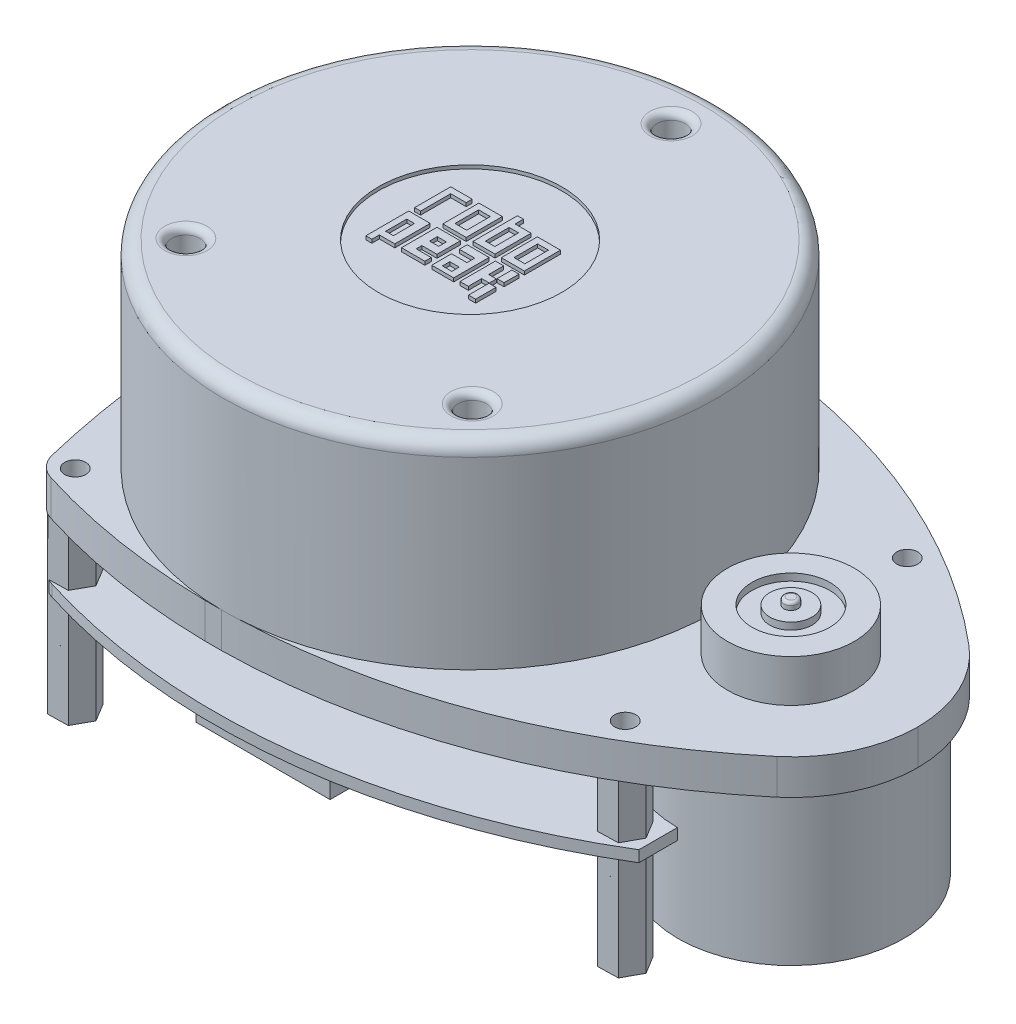
SolidWorks part; units mm, degrees
ref_plane "Спереди" through (0, 0, 0) normal (0, 0, 1) x (1, 0, 0)
ref_plane "Сверху" through (0, 0, 0) normal (0, 1, 0) x (1, 0, 0)
ref_plane "Справа" through (0, 0, 0) normal (1, 0, 0) x (0, 0, -1)
sketch "Эскиз1" plane through (0, 0, 0) normal (0, 1, 0) x (1, 0, 0)
  line L1 (-49.25, 35) -> (49.25, 35)
  line L2 (-49.25, 35) -> (-49.25, -35)
  line L3 (-49.25, -35) -> (49.25, -35)
  line L4 (49.25, 35) -> (49.25, -35)
  line L5 (-49.25, 35) -> (49.25, -35) construction
  line L6 (-49.25, -35) -> (49.25, 35) construction
  point P0 (0, 0)
  dimension "D1" = 98.5
  dimension "D2" = 70
extrude "Бобышка-Вытянуть1" add sketch "Эскиз1" along normal blind 5
sketch "Эскиз2" plane through (0, 5, 0) normal (0, 1, 0) x (1, 0, 0)
  line L0 (-49.25, 35) -> (-49.25, -35) construction
  circle A0 centre (-14.25, 0) radius 35
  point P2 (-49.25, 0)
  point P3 (-49.25, 0)
extrude "Бобышка-Вытянуть2" add sketch "Эскиз2" along normal blind 28.1
sketch "Эскиз3" plane through (0, 33.1, 0) normal (0, 1, 0) x (1, 0, 0)
  line L0 (-14.25, 0) -> (-14.25, 50000) construction
  line L1 (-14.25, -20) -> (-26.2883, -20) construction
  line L2 (-49.25, -35) -> (-14.25, -35) construction
  circle A0 centre (-14.25, 28.5) radius 2
  circle A1 centre (-34.5539, -20) radius 2
  circle A2 centre (6.0539, -20) radius 2
  arc A3 (-49.25, 0) -> (-14.25, -35) centre (-14.25, 0) ccw construction
  circle A4 centre (-14.25, 0) radius 35 construction
  dimension "D2" = 4
  dimension "D1" = 6.5
  dimension "D3" = 15
  dimension "D4" = 28.5
  dimension "D5" = 28.5
extrude "Вырез-Вытянуть1" cut sketch "Эскиз3" against normal blind 5
fillet "Скругление1" radius 2 1 edges at (-14.25, 33.1, 35)
fillet "Скругление2" radius 1 3 edges at (6.0539, 33.1, 22) (-34.5539, 33.1, 22) (-14.25, 33.1, -26.5)
sketch "Эскиз4" plane through (0, 33.1, 0) normal (0, 1, 0) x (1, 0, 0)
  line L0 (-22.1152, -6.9149) -> (-22.1152, -0.8316)
  line L1 (-22.1152, -0.8316) -> (-19.0735, -0.8316)
  line L2 (-19.0735, -0.8316) -> (-19.0735, -5.8538)
  line L3 (-19.0735, -5.8538) -> (-21.2663, -5.8538)
  line L4 (-21.2663, -5.8538) -> (-21.2663, -6.9149)
  line L5 (-21.2663, -6.9149) -> (-22.1152, -6.9149)
  line L6 (-22.1152, 0) -> (-22.1152, 5.1201)
  line L7 (-22.1152, 5.1201) -> (-19.0735, 5.1201)
  line L8 (-19.0735, 5.1201) -> (-19.0735, 4.2707)
  line L9 (-19.0735, 4.2707) -> (-21.2663, 4.2707)
  line L10 (-21.2663, 4.2707) -> (-21.2663, 0)
  line L11 (-21.2663, 0) -> (-22.1152, 0)
  line L12 (-21.2663, -1.9579) -> (-20.1699, -1.9579)
  line L13 (-20.1699, -1.9579) -> (-20.1699, -4.9509)
  line L14 (-20.1699, -4.9509) -> (-21.2663, -4.9509)
  line L15 (-21.2663, -4.9509) -> (-21.2663, -1.9579)
  line L16 (-13.8296, 0) -> (-13.8296, 6.293)
  line L17 (-18.1168, 0) -> (-14.8003, 0)
  line L18 (-18.1168, 0) -> (-18.1168, 5.1201)
  line L19 (-18.1168, 5.1201) -> (-14.8003, 5.1201)
  line L20 (-14.8003, 0) -> (-14.8003, 5.1201)
  line L21 (-9.8255, 5.1201) -> (-6.5494, 5.1201)
  line L22 (-9.8255, 5.1201) -> (-9.8255, 0)
  line L23 (-9.8255, 0) -> (-6.5494, 0)
  line L24 (-6.5494, 5.1201) -> (-6.5494, 0)
  line L25 (-8.9357, 4.2707) -> (-7.3988, 4.2707)
  line L26 (-8.9357, 4.2707) -> (-8.9357, 0.9137)
  line L27 (-8.9357, 0.9137) -> (-7.3988, 0.9137)
  line L28 (-7.3988, 4.2707) -> (-7.3988, 0.9137)
  line L29 (-17.3079, 4.2707) -> (-15.6497, 4.2707)
  line L30 (-17.3079, 4.2707) -> (-17.3079, 0.9137)
  line L31 (-17.3079, 0.9137) -> (-15.6497, 0.9137)
  line L32 (-15.6497, 4.2707) -> (-15.6497, 0.9137)
  line L33 (-12.9802, 4.2707) -> (-11.6455, 4.2707)
  line L34 (-12.9802, 4.2707) -> (-12.9802, 0.9137)
  line L35 (-12.9802, 0.9137) -> (-11.6455, 0.9137)
  line L36 (-11.6455, 4.2707) -> (-11.6455, 0.9137)
  line L37 (-12.9802, -4.142) -> (-11.6455, -4.142)
  line L38 (-12.9802, -4.142) -> (-12.9802, -5.1936)
  line L39 (-12.9802, -5.1936) -> (-11.6455, -5.1936)
  line L40 (-11.6455, -4.142) -> (-11.6455, -5.1936)
  line L41 (-16.9439, -1.9579) -> (-15.6497, -1.9579)
  line L42 (-16.9439, -1.9579) -> (-16.9439, -3.0499)
  line L43 (-16.9439, -3.0499) -> (-15.6497, -3.0499)
  line L44 (-15.6497, -1.9579) -> (-15.6497, -3.0499)
  line L46 (-7.5508, -0.7643) -> (-6.5494, -0.7643)
  line L47 (-7.5508, -0.7643) -> (-7.5508, -2.8858)
  line L48 (-7.5508, -2.8858) -> (-6.5494, -2.8858)
  line L49 (-6.5494, -0.7643) -> (-6.5494, -2.8858)
  line L50 (-6.5494, -6.9149) -> (-7.5508, -6.9149)
  line L51 (-6.5494, -6.9149) -> (-6.5494, -4.0216)
  line L52 (-6.5494, -4.0216) -> (-7.5508, -4.0216)
  line L53 (-13.8296, 6.293) -> (-12.9802, 6.293)
  line L54 (-12.9802, 6.293) -> (-12.9802, 5.1201)
  line L55 (-12.9802, 5.1201) -> (-10.7153, 5.1201)
  line L56 (-10.7153, 5.1201) -> (-10.7153, 0)
  line L57 (-10.7153, 0) -> (-13.8296, 0)
  line L58 (-9.8255, -0.8316) -> (-8.6437, -0.8316)
  line L59 (-8.6437, -0.8316) -> (-8.6437, -2.9608)
  line L60 (-8.6437, -2.9608) -> (-7.5508, -2.9608)
  line L61 (-9.8255, -0.8316) -> (-9.8255, -5.8538)
  line L62 (-9.8255, -5.8538) -> (-8.6437, -5.8538)
  line L63 (-8.6437, -5.8538) -> (-8.6437, -3.9573)
  line L64 (-8.6437, -3.9573) -> (-7.5508, -3.9573)
  line L65 (-7.5508, -2.9608) -> (-7.5508, -3.9573)
  line L66 (-13.8296, -0.8316) -> (-10.7153, -0.8316)
  line L67 (-10.7153, -0.8316) -> (-10.7153, -5.8538)
  line L68 (-10.7153, -5.8538) -> (-13.8296, -5.8538)
  line L69 (-13.8296, -5.8538) -> (-13.8296, -3.0499)
  line L70 (-13.8296, -3.0499) -> (-11.6455, -3.0499)
  line L71 (-11.6455, -3.0499) -> (-11.6455, -1.9408)
  line L72 (-11.6455, -1.9408) -> (-13.8296, -1.9408)
  line L73 (-13.8296, -1.9408) -> (-13.8296, -0.8316)
  line L74 (-18.1168, -0.8316) -> (-14.8003, -0.8316)
  line L75 (-14.8003, -0.8316) -> (-14.8003, -4.142)
  line L76 (-14.8003, -4.142) -> (-16.9439, -4.142)
  line L77 (-16.9439, -4.142) -> (-16.9439, -4.9509)
  line L78 (-16.9439, -4.9509) -> (-14.8003, -4.9509)
  line L79 (-14.8003, -4.9509) -> (-14.8003, -5.8538)
  line L80 (-14.8003, -5.8538) -> (-18.1168, -5.8538)
  line L81 (-18.1168, -5.8538) -> (-18.1168, -0.8316)
  line L82 (-7.5508, -6.9149) -> (-7.5508, -4.0216)
  circle A0 centre (-14.25, 0) radius 13
  dimension "D1" = 26
extrude "Вырез-Вытянуть3" cut sketch "Эскиз4" against normal blind 0.5 contours A0 L50 L82 L52 L51 L72 L73 L66 L67 L68 L69 L70 L71 L56 L57 L16 L53 L54 L55 L10 L11 L6 L7 L8 L9 L4 L5 L0 L1 L2 L3 L20 L17 L18 L19 L21 L24 L23 L22 L46 L49 L48 L47 | L32 L29 L30 L31 | L36 L33 L34 L35 | L28 L25 L26 L27 | L44 L41 L42 L43 | L15 L14 L13 L12 | L37 L40 L39 L38 region at (-20.7181, 33.1, 3.4544) region at (-8.1672, 33.1, -2.5922) region at (-16.4788, 33.1, -2.5922) region at (-12.3129, 33.1, -2.5922) region at (-16.2968, 33.1, 2.5039) region at (-14.2871, 33.1, -0.0991)
sketch "Эскиз5" plane through (0, 5, 0) normal (0, 1, 0) x (1, 0, 0)
  line L0 (-42.25, 30.7255) -> (-42.25, -39.5827) construction
  line L1 (27.75, 26.9972) -> (27.75, -49973.0028) construction
  line L2 (-49.25, 0) -> (49950.75, 0) construction
  circle A0 centre (-14.25, 0) radius 33 construction
  circle A1 centre (-42.25, 28) radius 1.25
  circle A2 centre (27.75, 20) radius 1.25
  circle A3 centre (27.75, -20) radius 1.25
  circle A4 centre (-42.25, -28) radius 1.25
  point P4 (-14.25, 33)
  dimension "D1" = 28
  dimension "D3" = 2.5
  dimension "D2" = 42
  dimension "D4" = 28
  dimension "D5" = 20
extrude "Вырез-Вытянуть4" cut sketch "Эскиз5" against normal blind 5
sketch "Эскиз6" plane through (0, 5, 0) normal (0, 1, 0) x (1, 0, 0)
  line L0 (49.25, 0) -> (50049.25, 0) construction
  line L1 (49.25, -35) -> (49.25, 35) construction
  circle A0 centre (31.25, 0) radius 9
  arc A1 (-14.25, -35) -> (-14.25, 35) centre (-14.25, 0) ccw construction
  point P4 (49.25, 0)
  dimension "D1" = 18
  dimension "D2" = 45.5
extrude "Бобышка-Вытянуть3" add sketch "Эскиз6" along normal blind 7
sketch "Эскиз7" plane through (0, 12, 0) normal (0, 1, 0) x (1, 0, 0)
  circle A0 centre (31.25, 0) radius 9
  circle A1 centre (31.25, 0) radius 0.9935
extrude "Вырез-Вытянуть5" cut sketch "Эскиз7" against normal blind 1
sketch "Эскиз8" plane through (0, 11, 0) normal (0, 1, 0) x (1, 0, 0)
  circle A0 centre (31.25, 0) radius 3.0011
  circle A1 centre (31.25, 0) radius 5.5217
extrude "Вырез-Вытянуть6" cut sketch "Эскиз8" against normal blind 1
fillet "Скругление3" radius 0.4 1 edges at (31.25, 12, 0.9935)
sketch "Эскиз9" plane through (0, 5, 0) normal (0, 1, 0) x (1, 0, 0)
  circle A0 centre (31.25, 0) radius 16
  dimension "D1" = 32
extrude "Бобышка-Вытянуть4" add sketch "Эскиз9" against normal blind 27
sketch "Эскиз10" plane through (0, 0, 0) normal (0, -1, 0) x (1, 0, 0)
  line L0 (-49.25, 0) -> (49950.75, 0) construction
  line L1 (-40.8546, 25.4729) -> (-39.3638, 27.9449)
  line L2 (-39.3638, 27.9449) -> (-40.7592, 30.472)
  line L3 (-40.7592, 30.472) -> (-43.6454, 30.5271)
  line L4 (-43.6454, 30.5271) -> (-45.1362, 28.0551)
  line L5 (-45.1362, 28.0551) -> (-43.7408, 25.528)
  line L6 (-43.7408, 25.528) -> (-40.8546, 25.4729)
  line L7 (29.2571, 22.4621) -> (26.3713, 22.5363)
  line L8 (26.3713, 22.5363) -> (24.8642, 20.0742)
  line L9 (24.8642, 20.0742) -> (26.2429, 17.5379)
  line L10 (26.2429, 17.5379) -> (29.1287, 17.4637)
  line L11 (29.1287, 17.4637) -> (30.6358, 19.9258)
  line L12 (30.6358, 19.9258) -> (29.2571, 22.4621)
  line L13 (30.6358, -19.9258) -> (29.2571, -22.4621)
  line L14 (29.1287, -17.4637) -> (30.6358, -19.9258)
  line L15 (26.2429, -17.5379) -> (29.1287, -17.4637)
  line L16 (24.8642, -20.0742) -> (26.2429, -17.5379)
  line L17 (26.3713, -22.5363) -> (24.8642, -20.0742)
  line L18 (29.2571, -22.4621) -> (26.3713, -22.5363)
  line L19 (-43.7408, -25.528) -> (-40.8546, -25.4729)
  line L20 (-45.1362, -28.0551) -> (-43.7408, -25.528)
  line L21 (-43.6454, -30.5271) -> (-45.1362, -28.0551)
  line L22 (-40.7592, -30.472) -> (-43.6454, -30.5271)
  line L23 (-39.3638, -27.9449) -> (-40.7592, -30.472)
  line L24 (-40.8546, -25.4729) -> (-39.3638, -27.9449)
  circle A0 centre (-42.25, 28) radius 2.5 construction
  circle A1 centre (27.75, 20) radius 2.5 construction
  circle A2 centre (27.75, -20) radius 2.5 construction
  circle A3 centre (-42.25, -28) radius 2.5 construction
  point P17 (27.75, 20)
  dimension "D1" = 5
  dimension "D2" = 5
extrude "Бобышка-Вытянуть5" add sketch "Эскиз10" along normal blind 24.6
sketch "Эскиз11" plane through (0, 5, 0) normal (0, 1, 0) x (1, 0, 0)
  circle A0 centre (-14.25, 0) radius 26
  dimension "D1" = 52
extrude "Бобышка-Вытянуть6" add sketch "Эскиз11" against normal blind 8
fillet "Скругление4" radius 1 1 edges at (-14.25, -3, 26)
sketch "Эскиз12" plane through (0, 5, 0) normal (0, 1, 0) x (1, 0, 0)
  line L1 (49.25, -35) -> (49.25, 35) construction
  line L2 (-49.25, 0) -> (-50049.25, 0) construction
  line L4 (-54.0511, 37.7308) -> (52.2004, 37.7308)
  line L5 (-54.0511, 37.7308) -> (-54.0511, -37.8351)
  line L6 (-54.0511, -37.8351) -> (52.2004, -37.8351)
  line L7 (52.2004, 37.7308) -> (52.2004, -37.8351)
  arc A0 (-49.25, 0) -> (-45.5286, 27.9743) centre (86.6751, -3.8473) cw
  circle A1 centre (-14.25, 0) radius 35 construction
  arc A3 (49.25, 0) -> (42.909, 13.5993) centre (31.4018, -0.0442) ccw
  arc A4 (-49.25, 0) -> (-14.25, -35) centre (-14.25, 0) ccw construction
  arc A5 (-42.835, 30.8555) -> (42.909, 13.5993) centre (-15.6796, -55.8665) cw
  arc A6 (-45.5286, 27.9743) -> (-42.835, 30.8555) centre (-41.6397, 27.0383) cw
  arc A7 (-45.5286, -27.9743) -> (-42.835, -30.8555) centre (-41.6397, -27.0383) ccw
  arc A8 (-42.835, -30.8555) -> (42.909, -13.5993) centre (-15.6796, 55.8665) ccw
  arc A9 (49.25, 0) -> (42.909, -13.5993) centre (31.4018, 0.0442) cw
  arc A10 (-49.25, 0) -> (-45.5286, -27.9743) centre (86.6751, 3.8473) ccw
  dimension "D1" = 4
extrude "Вырез-Вытянуть7" cut sketch "Эскиз12" against normal blind 8
fillet "Скругление5" radius 100 1 edges at (-49.25, 2.5, 0)
sketch "Эскиз13" plane through (0, 0, 0) normal (0, -1, 0) x (1, 0, 0)
  line L0 (31.5536, 21.8603) -> (31.5536, 16.4)
  line L1 (31.5536, -16.4) -> (31.5536, -21.8603)
  arc A0 (-49.0982, 0) -> (-45.3768, 27.9743) centre (86.8269, -3.8473) cw
  arc A1 (31.5536, 16.4) -> (31.5536, -16.4) centre (31.5536, 0) ccw
  arc A2 (-42.6831, 30.8555) -> (31.5536, 21.8603) centre (-15.5278, -55.8665) cw
  arc A3 (-45.3768, 27.9743) -> (-42.6831, 30.8555) centre (-41.4878, 27.0383) cw
  arc A4 (-45.3768, -27.9743) -> (-42.6831, -30.8555) centre (-41.4878, -27.0383) ccw
  arc A5 (-42.6831, -30.8555) -> (31.5536, -21.8603) centre (-15.5278, 55.8665) ccw
  arc A7 (-49.0982, 0) -> (-45.3768, -27.9743) centre (86.8269, 3.8473) ccw
  arc A8 (-48.5248, 10.6929) -> (-48.5248, -10.6929) centre (50.9018, 0) ccw construction
  point P16 (-49.0982, 0)
  point P21 (-49.0982, 0)
  dimension "D1" = 4
  dimension "D2" = 32.8
extrude "Бобышка-Вытянуть7" add sketch "Эскиз13" along normal blind 1.6 from offset 8
sketch "Эскиз14" plane through (0, -9.6, 0) normal (0, -1, 0) x (1, 0, 0)
  line L1 (-24.0982, 30) -> (-4.0982, 30)
  line L2 (-24.0982, 30) -> (-24.0982, 25)
  line L3 (-24.0982, 25) -> (-4.0982, 25)
  line L4 (-4.0982, 30) -> (-4.0982, 25)
  circle A0 centre (-14.25, 0) radius 35 construction
  point P4 (-14.0982, 30)
  dimension "D1" = 5
  dimension "D2" = 20
  dimension "D3" = 35
  dimension "D4" = 30
extrude "Бобышка-Вытянуть8" add sketch "Эскиз14" along normal blind 6
chamfer "Фаска1" distance 1 angle 45 1 edges at (-24.0982, -12.6, 30)
ref_plane "Plane1" through (0, -25, 0) normal (0, 1, 0) x (1, 0, 0)
sketch "Sketch1" plane through (0, -25, 0) normal (0, 1, 0) x (1, 0, 0)
  line L0 (-40.8546, -25.4729) -> (-43.6454, -30.5271) construction
  line L1 (-43.7408, 25.528) -> (-40.7592, 30.472) construction
  line L2 (24.8642, 20.0742) -> (30.6358, 19.9258) construction
  line L3 (24.8642, -20.0742) -> (30.6358, -19.9258) construction
  circle A0 centre (-42.25, -28) radius 1.5
  circle A1 centre (-42.25, 28) radius 1.5
  circle A2 centre (27.75, 20) radius 1.5
  circle A3 centre (27.75, -20) radius 1.5
  dimension "D1" = 3
  dimension "D2" = 3
  dimension "D3" = 3
  dimension "D4" = 3
extrude "Cut-Extrude1" cut sketch "Sketch1" along normal blind 30
